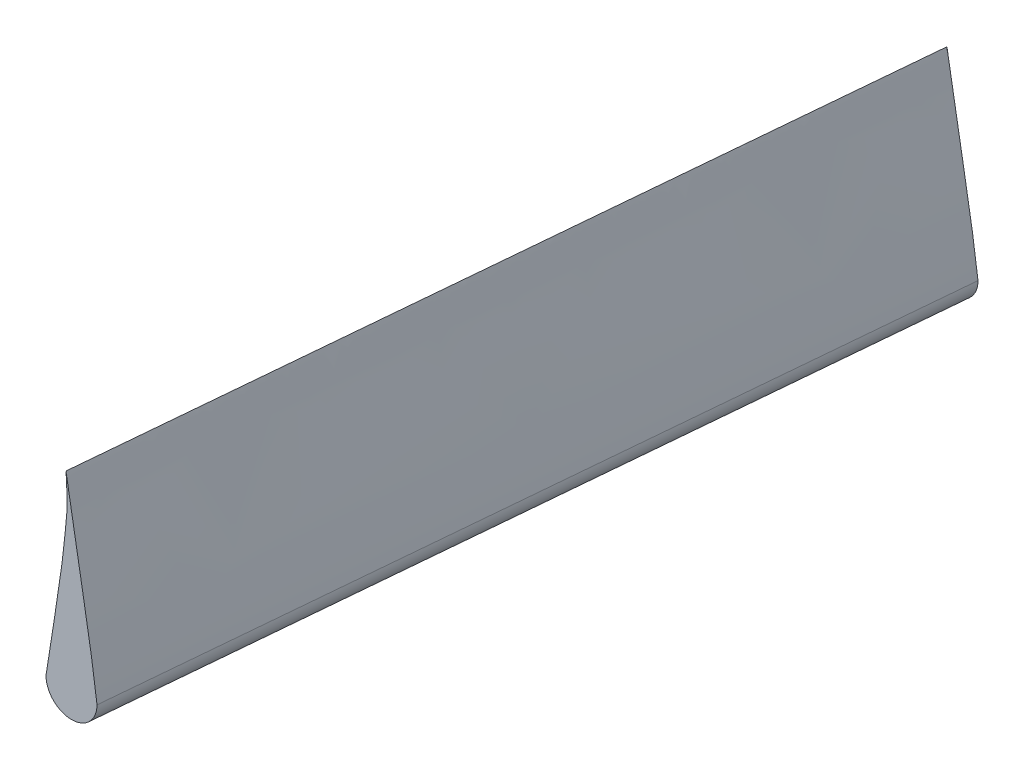
SolidWorks part; units mm, degrees
material "Choose your Material"
ref_plane "Front Plane" through (0, 0, 0) normal (0, 0, 1) x (1, 0, 0)
ref_plane "Top Plane" through (0, 0, 0) normal (0, 1, 0) x (1, 0, 0)
ref_plane "Right Plane" through (0, 0, 0) normal (1, 0, 0) x (0, 0, -1)
sketch "Sketch1" plane through (0, 0, 0) normal (0, 0, 1) x (1, 0, 0)
  arc A2 (-44.642, 1062.2575) -> (108.1631, 1062.2575) centre (31.7605, 1062.2575) ccw
  spline S2 degree 3 poles (108.1631, 1062.2575) (107.7965, 1065.2091) (104.5142, 1091.3228) (97.6923, 1140.5389) (86.89, 1209.8155) (75.1385, 1278.8671) (62.8377, 1348.1245) (50.6145, 1416.0185) (37.9388, 1488.4071) (28.1057, 1543.5686) (11.2614, 1662.8576) (21.4772, 1543.1341) (14.9163, 1487.3238) (8.6926, 1415.1266) (-0.7731, 1347.2963) (-10.5325, 1278.3247) (-21.5631, 1209.5038) (-32.4732, 1141.1151) (-40.1427, 1092.0503) (-44.1139, 1065.77) (-44.642, 1062.2575) knots 0.799627 0.799627 0.799627 0.799627 0.80279 0.827619 0.852472 0.877337 0.90219 0.927002 0.951758 0.976444 1.001125 1.025712 1.05027 1.074862 1.099032 1.124084 1.148678 1.17323 1.197721 1.201499 1.201499 1.201499 1.201499
sketch3d "3DSketch1"
  line L0 (108.1631, 1062.2575, 0) -> (110.607, 1283.6185, 2641.6)
sweep "Sweep1" add profiles "Sketch1" path "3DSketch1"
ref_point "Point1"
ref_point "Point2"
ref_axis "Axis1" through (31.7605, 1062.2575, 0) along (0.0009, 0.0835, 0.9965)
move or copy body "Body-Move/Copy1" [suppressed] bodies to move or copy 103
